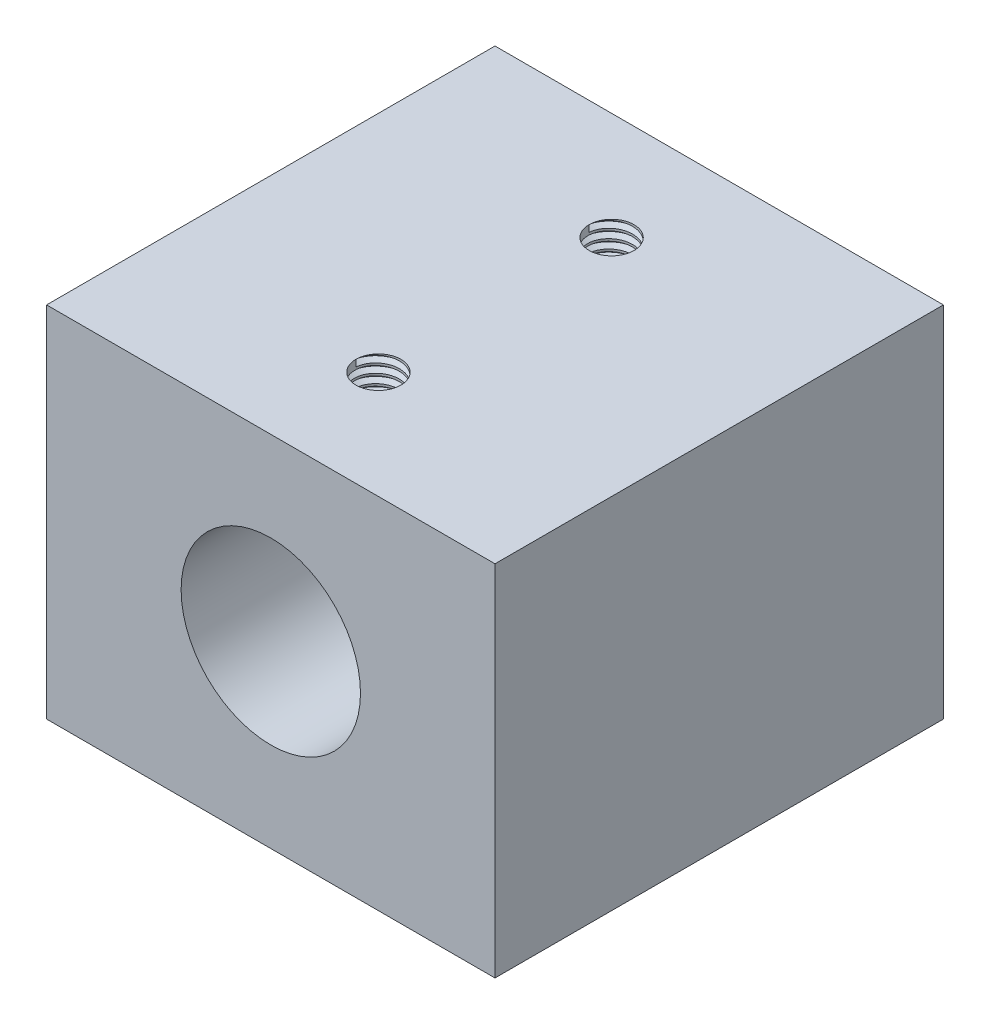
SolidWorks part; units mm, degrees
ref_plane "Front Plane" through (0, 0, 0) normal (0, 0, 1) x (1, 0, 0)
ref_plane "Top Plane" through (0, 0, 0) normal (0, 1, 0) x (1, 0, 0)
ref_plane "Right Plane" through (0, 0, 0) normal (1, 0, 0) x (0, 0, -1)
sketch "Sketch1" plane through (0, 0, 0) normal (0, 0, 1) x (1, 0, 0)
  line L1 (-12.5, 10) -> (12.5, 10)
  line L2 (-12.5, 10) -> (-12.5, -10)
  line L3 (-12.5, -10) -> (12.5, -10)
  line L4 (12.5, 10) -> (12.5, -10)
  line L5 (-12.5, 10) -> (12.5, -10) construction
  line L6 (-12.5, -10) -> (12.5, 10) construction
  circle A2 centre (0, 0) radius 5
  point P0 (0, 0)
  dimension "D3" = 10
  dimension "D1" = 20
  dimension "D2" = 25
extrude "Boss-Extrude1" add sketch "Sketch1" against normal blind 25
sketch "Sketch2" plane through (0, 10, 0) normal (0, 1, 0) x (1, 0, 0)
  line L0 (0, 19) -> (0, 6) construction
  line L1 (2, 19) -> (2, 6)
  line L2 (-2, 19) -> (-2, 6)
  line L4 (-55, 0) -> (55, 0) construction
  arc A0 (2, 19) -> (-2, 19) centre (0, 19) ccw
  arc A1 (-2, 6) -> (2, 6) centre (0, 6) ccw
  point P3 (0, 12.5)
  point P12 (0, 19)
  point P14 (0, 6)
  dimension "D2" = 4
  dimension "D3" = 6
  dimension "D1" = 13
hole_wizard "M3 Tapped Hole1" positions "Sketch2" profile "Sketch3" tap size "M3" standard "DIN"
sketch "Sketch3" plane through (0, 10, -6) normal (1, 0, 0) x (0, 0, 1)
  line L0 (0, 0) -> (0, 9.2511)
  line L1 (0, 9.2511) -> (1.25, 8.5)
  line L2 (1.25, 8.5) -> (1.25, 0)
  line L5 (1.25, 0) -> (0, 0)
  line L10 (0, 9.2511) -> (-1.25, 8.5) construction
  line L11 (0, -6.35) -> (0, 107.95) construction
  dimension "Tap Drill Dia." = 2.5
  dimension "Tap Drill Depth" = 8.5
  dimension "Drill Angle" = 118
cosmetic thread "Hole Thread1"
cosmetic thread "Hole Thread2"
thread "Thread1" pitch 0.5 start angle 0, offset 0, length 10, pitch 0.5, diameter 2.5
ref_plane "Plane1" through (-1.25, 10, -19) normal (0, 0, 1) x (-1, 0, 0)
sketch "Thread Profile1" plane through (-1.25, 10, -19) normal (0, 0, 1) x (-1, 0, 0)
  line L0 (0, 0) -> (0, 0.5) construction
  line L1 (0, 0) -> (0.2706, 0.1562)
  line L2 (0.2706, 0.1562) -> (0.2706, 0.2187)
  line L3 (0.2706, 0.2187) -> (0, 0.375)
  line L4 (0.2706, 0.1875) -> (0, 0.1875) construction
  line L11 (0, 0) -> (0, 0.375)
  point P2 (0, 0)
  dimension "Pitch" = 0.5
  dimension "Profile_Angle" = 60
  dimension "Profile_Land" = 0.0625
  dimension "Profile_Height" = 0.2706
thread "Thread2" pitch 0.5 profile "Thread Profile2" start angle 0, offset 0, length 10, pitch 0.5, diameter 2.5
ref_plane "Plane2" through (-1.25, 10, -6) normal (0, 0, 1) x (-1, 0, 0)
sketch "Thread Profile2" plane through (-1.25, 10, -6) normal (0, 0, 1) x (-1, 0, 0)
  line L0 (0, 0) -> (0, 0.5) construction
  line L1 (0, 0) -> (0.2706, 0.1562)
  line L2 (0.2706, 0.1562) -> (0.2706, 0.2187)
  line L3 (0.2706, 0.2187) -> (0, 0.375)
  line L4 (0.2706, 0.1875) -> (0, 0.1875) construction
  line L11 (0, 0) -> (0, 0.375)
  point P2 (0, 0)
  dimension "Pitch" = 0.5
  dimension "Profile_Angle" = 60
  dimension "Profile_Land" = 0.0625
  dimension "Profile_Height" = 0.2706
